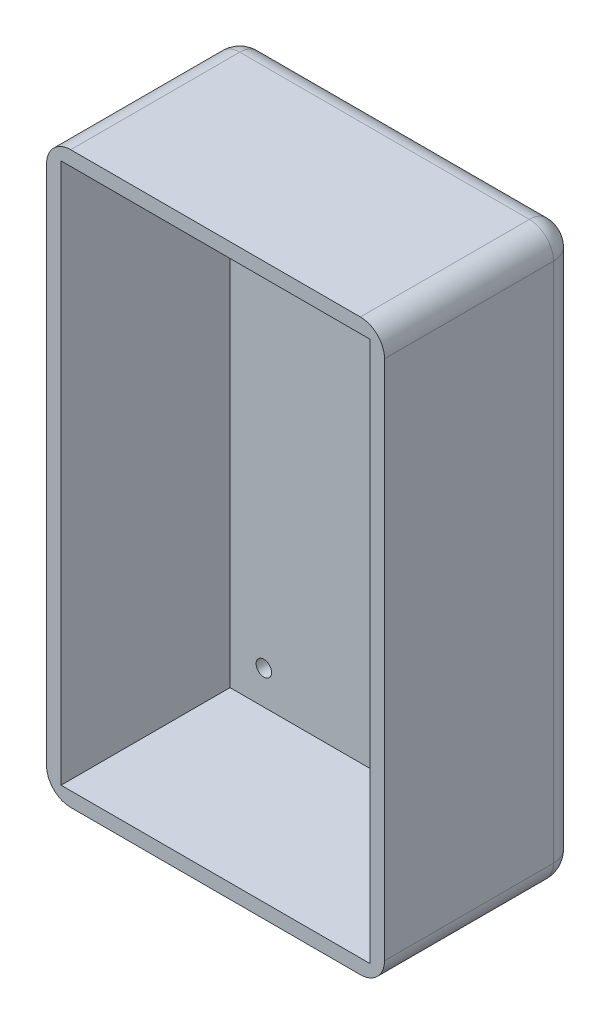
SolidWorks part; units mm, degrees
ref_plane "正面" through (0, 0, 0) normal (0, 0, 1) x (1, 0, 0)
ref_plane "平面" through (0, 0, 0) normal (0, 1, 0) x (1, 0, 0)
ref_plane "右側面" through (0, 0, 0) normal (1, 0, 0) x (0, 0, -1)
sketch "ｽｹｯﾁ1" plane through (0, 0, 0) normal (0, 0, 1) x (1, 0, 0)
  line L1 (-35, -59) -> (35, -59)
  line L2 (-35, -59) -> (-35, 59)
  line L3 (-35, 59) -> (35, 59)
  line L4 (35, -59) -> (35, 59)
  line L5 (-35, -59) -> (35, 59) construction
  line L6 (-35, 59) -> (35, -59) construction
  point P0 (0, 0)
  dimension "D1" = 118
  dimension "D2" = 70
extrude "ﾎﾞｽ - 押し出し1" add sketch "ｽｹｯﾁ1" along normal blind 40
sketch "ｽｹｯﾁ2" plane through (0, 0, 40) normal (0, 0, 1) x (1, 0, 0)
  line L1 (-32, -56) -> (32, -56)
  line L2 (-32, -56) -> (-32, 56)
  line L3 (-32, 56) -> (32, 56)
  line L4 (32, -56) -> (32, 56)
  line L5 (-32, -56) -> (32, 56) construction
  line L6 (-32, 56) -> (32, -56) construction
  point P0 (0, 0)
  dimension "D1" = 112
  dimension "D2" = 64
extrude "ｶｯﾄ - 押し出し1" cut sketch "ｽｹｯﾁ2" against normal blind 35
sketch "ｽｹｯﾁ3" plane through (0, 0, 5) normal (0, 0, 1) x (1, 0, 0)
  line L1 (-25, -49) -> (25, -49) construction
  line L2 (-25, -49) -> (-25, 49) construction
  line L3 (-25, 49) -> (25, 49) construction
  line L4 (25, -49) -> (25, 49) construction
  line L5 (-25, -49) -> (25, 49) construction
  line L6 (-25, 49) -> (25, -49) construction
  circle A0 centre (-25, 49) radius 1.6
  circle A1 centre (25, 49) radius 1.6
  circle A2 centre (-25, -49) radius 1.6
  circle A3 centre (25, -49) radius 1.6
  point P0 (0, 0)
  dimension "D1" = 50
  dimension "D2" = 98
  dimension "D3" = 3.2
  dimension "D4" = 3.2
  dimension "D5" = 3.2
  dimension "D6" = 3.2
extrude "ｶｯﾄ - 押し出し2" cut sketch "ｽｹｯﾁ3" against normal through all
fillet "ﾌｨﾚｯﾄ1" radius 5 4 edges at (0, -59, 0) (0, 59, 0) (-35, 0, 0) (35, 0, 0)
fillet "ﾌｨﾚｯﾄ2" radius 5 8 edges at (-33.5355, 57.5355, 1.4645) (-33.5355, -57.5355, 1.4645) (33.5355, 57.5355, 1.4645) (33.5355, -57.5355, 1.4645) (-35, 59, 22.5) (-35, -59, 22.5) (35, 59, 22.5) (35, -59, 22.5)
